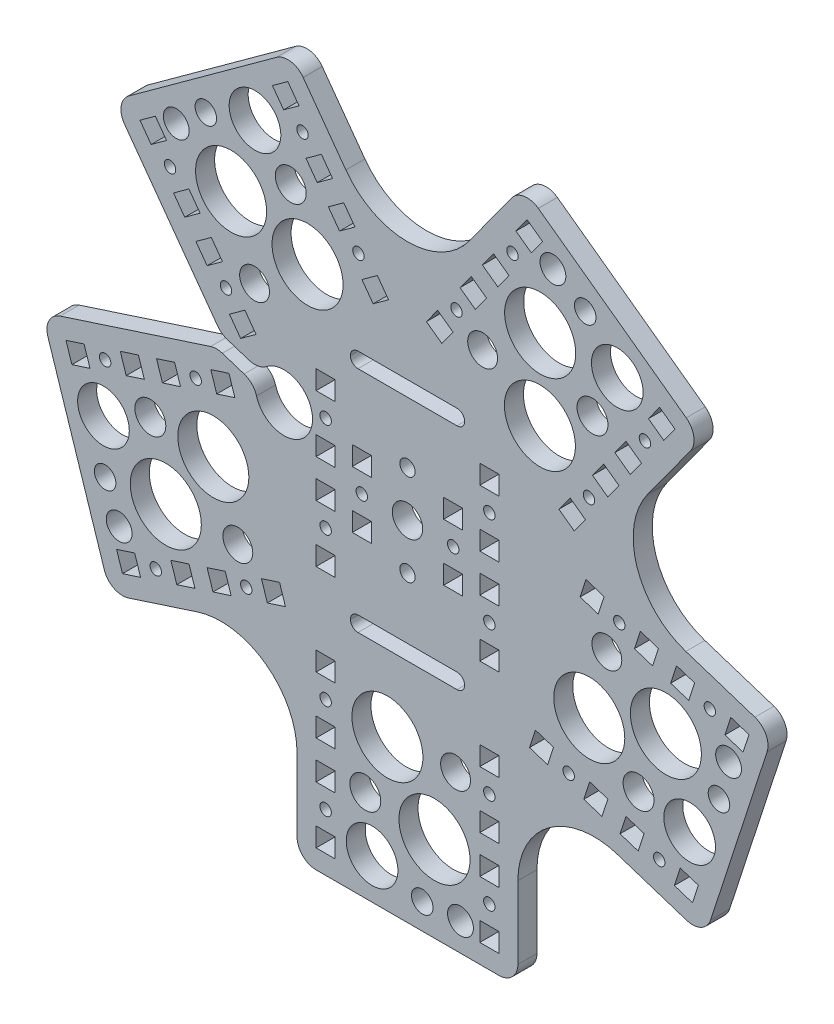
SolidWorks part; units mm, degrees
ref_plane "Plan de face" through (0, 0, 0) normal (0, 0, 1) x (1, 0, 0)
ref_plane "Plan de dessus" through (0, 0, 0) normal (0, 1, 0) x (1, 0, 0)
ref_plane "Plan de droite" through (0, 0, 0) normal (1, 0, 0) x (0, 0, -1)
sketch "Esquisse1" plane through (0, 0, 0) normal (0, 0, 1) x (1, 0, 0)
  line L0 (0, 0) -> (17.8582, 0) construction
  line L1 (-20, 40) -> (20, 40) construction
  line L2 (20, 40) -> (20, -40) construction
  line L3 (20, -40) -> (-20, -40) construction
  line L4 (-20, -40) -> (-20, 40) construction
  line L13 (0, 0) -> (0, 13.4404) construction
  line L16 (-20, -40) -> (-20, 40) construction
  line L18 (0, -40) -> (0, 40) construction
  line L19 (-15, -32) -> (-15, -28)
  line L20 (-15, 32) -> (15, 32)
  line L21 (-15, 32) -> (-15, 28)
  line L22 (-15, 28) -> (15, 28)
  line L23 (15, 32) -> (15, 28)
  line L24 (-15, -28) -> (15, -28)
  line L25 (15, -32) -> (15, -28)
  line L26 (-15, -32) -> (15, -32)
  line L27 (-29, -91.5) -> (29, -91.5)
  line L28 (29, -91.5) -> (29, -39.9151)
  line L29 (-29, -91.5) -> (-29, -39.9151)
  line L30 (-78.0602, -55.8557) -> (-29, -39.9151)
  line L31 (-95.9832, -0.6944) -> (-78.0602, -55.8557)
  line L32 (-95.9832, -0.6944) -> (-46.923, 15.2462) construction
  line L33 (-77.2438, 56.9793) -> (-46.923, 15.2462) construction
  line L34 (-30.3209, 91.0708) -> (-77.2438, 56.9793)
  line L35 (-30.3209, 91.0708) -> (0, 49.3377)
  line L36 (30.3209, 91.0708) -> (0, 49.3377)
  line L37 (77.2438, 56.9793) -> (30.3209, 91.0708)
  line L38 (77.2438, 56.9793) -> (46.923, 15.2462)
  line L39 (95.9832, -0.6944) -> (46.923, 15.2462)
  line L40 (78.0602, -55.8557) -> (95.9832, -0.6944)
  line L41 (78.0602, -55.8557) -> (29, -39.9151)
  line L42 (-15, 40) -> (15, 40) construction
  line L43 (-15, 40) -> (-15, 36) construction
  line L44 (-15, 36) -> (15, 36) construction
  line L45 (15, 40) -> (15, 36) construction
  line L46 (-15, -40) -> (-15, -36) construction
  line L47 (-15, -40) -> (15, -40) construction
  line L48 (15, -40) -> (15, -36) construction
  line L49 (-15, -36) -> (15, -36) construction
  line L50 (-77.2438, 56.9793) -> (-48.923, 17.999)
  line L51 (-48.923, 17.999) -> (-38.6965, 14.6762)
  line L52 (-38.6965, 14.6762) -> (-39.9326, 10.872) construction
  line L53 (-39.9326, 10.872) -> (-50.1591, 14.1947)
  line L54 (-50.1591, 14.1947) -> (-95.9832, -0.6944)
  line L55 (-46.923, 15.2462) -> (-39.3145, 12.7741) construction
  arc A0 (-38.6965, 14.6762) -> (-39.9326, 10.872) centre (-32.4399, 10.5404) cw
  circle A1 centre (0, 0) radius 4
  circle A2 centre (12, 0) radius 2 construction
  circle A3 centre (0, -12) radius 2
  circle A4 centre (-12, 0) radius 2 construction
  circle A5 centre (0, 12) radius 2
  circle A6 centre (-5.2713, -51.9057) radius 9.3306
  circle A7 centre (7.0906, -69.0484) radius 9.3306
  circle A8 centre (-9.3008, -80.9322) radius 6.7851
  circle A9 centre (-11.0766, -67.4093) radius 4.0624
  circle A10 centre (12.6227, -50.9495) radius 3.924
  circle A11 centre (3.8806, -84.7569) radius 2.83
  circle A12 centre (13.9204, -84.1422) radius 3.3916
  circle A13 centre (-75.7223, -39.2404) radius 3.3916
  circle A14 centre (-79.4094, -29.882) radius 2.83
  circle A15 centre (-79.8452, -16.1638) radius 6.7851
  circle A16 centre (-67.5329, -10.2962) radius 4.0624
  circle A17 centre (-50.9942, -11.0265) radius 9.3306
  circle A18 centre (-44.5553, -27.7492) radius 3.924
  circle A19 centre (-63.4778, -28.0807) radius 9.3306
  circle A20 centre (-60.7194, 59.8903) radius 3.3916
  circle A21 centre (-52.9583, 66.2888) radius 2.83
  circle A22 centre (-40.0462, 70.9424) radius 6.7851
  circle A23 centre (-30.661, 61.0459) radius 4.0624
  circle A24 centre (-26.2449, 45.091) radius 9.3306
  circle A25 centre (-40.1594, 33.7996) radius 3.924
  circle A26 centre (-46.3221, 51.6936) radius 9.3306
  circle A27 centre (38.1957, 76.2547) radius 3.3916
  circle A28 centre (46.6794, 70.8507) radius 2.83
  circle A29 centre (55.0953, 60.0086) radius 6.7851
  circle A30 centre (48.5833, 48.0246) radius 4.0624
  circle A31 centre (34.774, 38.8942) radius 9.3306
  circle A32 centre (19.7354, 48.6385) radius 3.924
  circle A33 centre (34.8492, 60.0291) radius 9.3306
  circle A34 centre (84.3256, -12.7623) radius 3.3916
  circle A35 centre (81.8078, -22.5006) radius 2.83
  circle A36 centre (74.097, -33.855) radius 6.7851
  circle A37 centre (60.6872, -31.3651) radius 4.0624
  circle A38 centre (47.7363, -21.053) radius 9.3306
  circle A39 centre (52.3565, -3.7394) radius 3.924
  circle A40 centre (67.8601, -14.5936) radius 9.3306
  point P12 (0, 0)
  point P19 (0, 0)
  point P32 (-37.6183, 51.7771)
  point P42 (0, 0)
  point P56 (0, 0)
  point P64 (0, 0)
  point P85 (0, 0)
  point P134 (0, 0)
  line B0 (-24, -71.5) -> (-24, -66.5)
  line B1 (-24, -71.5) -> (-19, -71.5)
  line B2 (-19, -71.5) -> (-19, -66.5)
  line B3 (-24, -66.5) -> (-19, -66.5)
  line B4 (-24, -81.5) -> (-24, -86.5)
  line B5 (-24, -81.5) -> (-19, -81.5)
  line B6 (-19, -81.5) -> (-19, -86.5)
  line B7 (-24, -86.5) -> (-19, -86.5)
  circle B8 centre (-21.5, -76.5) radius 1.5
  line B9 (-24, -56.5) -> (-24, -61.5)
  line B10 (-24, -56.5) -> (-19, -56.5)
  line B11 (-19, -56.5) -> (-19, -61.5)
  line B12 (-24, -61.5) -> (-19, -61.5)
  line B13 (-24, -46.5) -> (-24, -41.5)
  line B14 (-24, -46.5) -> (-19, -46.5)
  line B15 (-19, -46.5) -> (-19, -41.5)
  line B16 (-24, -41.5) -> (-19, -41.5)
  circle B17 centre (-21.5, -51.5) radius 1.5
  line B18 (24, -56.5) -> (24, -61.5)
  line B19 (24, -56.5) -> (19, -56.5)
  line B20 (19, -56.5) -> (19, -61.5)
  line B21 (24, -61.5) -> (19, -61.5)
  line B22 (24, -46.5) -> (24, -41.5)
  line B23 (24, -46.5) -> (19, -46.5)
  line B24 (19, -46.5) -> (19, -41.5)
  line B25 (24, -41.5) -> (19, -41.5)
  circle B26 centre (21.5, -51.5) radius 1.5
  line B27 (24, -71.5) -> (24, -66.5)
  line B28 (24, -71.5) -> (19, -71.5)
  line B29 (19, -71.5) -> (19, -66.5)
  line B30 (24, -66.5) -> (19, -66.5)
  line B31 (24, -81.5) -> (24, -86.5)
  line B32 (24, -81.5) -> (19, -81.5)
  line B33 (19, -81.5) -> (19, -86.5)
  line B34 (24, -86.5) -> (19, -86.5)
  circle B35 centre (21.5, -76.5) radius 1.5
  line B36 (24, -86.5) -> (-24, -86.5) construction
  line B37 (0, -86.5) -> (0, -41.5) construction
  line B38 (-75.4169, 0.7306) -> (-70.6617, 2.2757)
  line B39 (-75.4169, 0.7306) -> (-73.8719, -4.0246)
  line B40 (-73.8719, -4.0246) -> (-69.1166, -2.4796)
  line B41 (-70.6617, 2.2757) -> (-69.1166, -2.4796)
  line B42 (-84.9275, -2.3595) -> (-89.6828, -3.9046)
  line B43 (-84.9275, -2.3595) -> (-83.3824, -7.1148)
  line B44 (-83.3824, -7.1148) -> (-88.1377, -8.6599)
  line B45 (-89.6828, -3.9046) -> (-88.1377, -8.6599)
  circle B46 centre (-79.3997, -3.1921) radius 1.5
  line B47 (-61.1511, 5.3659) -> (-65.9064, 3.8208)
  line B48 (-61.1511, 5.3659) -> (-59.606, 0.6106)
  line B49 (-59.606, 0.6106) -> (-64.3613, -0.9345)
  line B50 (-65.9064, 3.8208) -> (-64.3613, -0.9345)
  line B51 (-51.6405, 8.4561) -> (-46.8853, 10.0012)
  line B52 (-51.6405, 8.4561) -> (-50.0955, 3.7008)
  line B53 (-50.0955, 3.7008) -> (-45.3402, 5.2459)
  line B54 (-46.8853, 10.0012) -> (-45.3402, 5.2459)
  circle B55 centre (-55.6233, 4.5333) radius 1.5
  line B56 (-46.3183, -40.2848) -> (-51.0736, -41.8299)
  line B57 (-46.3183, -40.2848) -> (-47.8634, -35.5295)
  line B58 (-47.8634, -35.5295) -> (-52.6187, -37.0746)
  line B59 (-51.0736, -41.8299) -> (-52.6187, -37.0746)
  line B60 (-36.8077, -37.1946) -> (-32.0524, -35.6496)
  line B61 (-36.8077, -37.1946) -> (-38.3528, -32.4394)
  line B62 (-38.3528, -32.4394) -> (-33.5975, -30.8943)
  line B63 (-32.0524, -35.6496) -> (-33.5975, -30.8943)
  circle B64 centre (-42.3355, -36.3621) radius 1.5
  line B65 (-60.5841, -44.9201) -> (-55.8289, -43.375)
  line B66 (-60.5841, -44.9201) -> (-62.1292, -40.1648)
  line B67 (-62.1292, -40.1648) -> (-57.3739, -38.6197)
  line B68 (-55.8289, -43.375) -> (-57.3739, -38.6197)
  line B69 (-70.0947, -48.0102) -> (-74.85, -49.5553)
  line B70 (-70.0947, -48.0102) -> (-71.6398, -43.255)
  line B71 (-71.6398, -43.255) -> (-76.3951, -44.8)
  line B72 (-74.85, -49.5553) -> (-76.3951, -44.8)
  circle B73 centre (-66.112, -44.0875) radius 1.5
  line B74 (-22.6102, 71.9516) -> (-19.6713, 67.9065)
  line B75 (-22.6102, 71.9516) -> (-26.6553, 69.0126)
  line B76 (-26.6553, 69.0126) -> (-23.7164, 64.9675)
  line B77 (-19.6713, 67.9065) -> (-23.7164, 64.9675)
  line B78 (-28.4881, 80.0417) -> (-31.427, 84.0868)
  line B79 (-28.4881, 80.0417) -> (-32.5332, 77.1028)
  line B80 (-32.5332, 77.1028) -> (-35.4721, 81.1479)
  line B81 (-31.427, 84.0868) -> (-35.4721, 81.1479)
  circle B82 centre (-27.5717, 74.5272) radius 1.5
  line B83 (-13.7935, 59.8163) -> (-16.7324, 63.8614)
  line B84 (-13.7935, 59.8163) -> (-17.8385, 56.8774)
  line B85 (-17.8385, 56.8774) -> (-20.7775, 60.9225)
  line B86 (-16.7324, 63.8614) -> (-20.7775, 60.9225)
  line B87 (-7.9156, 51.7261) -> (-4.9767, 47.6811)
  line B88 (-7.9156, 51.7261) -> (-11.9607, 48.7872)
  line B89 (-11.9607, 48.7872) -> (-9.0218, 44.7421)
  line B90 (-4.9767, 47.6811) -> (-9.0218, 44.7421)
  circle B91 centre (-12.8771, 54.3018) radius 1.5
  line B92 (-52.6263, 31.6026) -> (-55.5652, 35.6477)
  line B93 (-52.6263, 31.6026) -> (-48.5812, 34.5415)
  line B94 (-48.5812, 34.5415) -> (-51.5201, 38.5866)
  line B95 (-55.5652, 35.6477) -> (-51.5201, 38.5866)
  line B96 (-46.7484, 23.5124) -> (-43.8095, 19.4674)
  line B97 (-46.7484, 23.5124) -> (-42.7033, 26.4514)
  line B98 (-42.7033, 26.4514) -> (-39.7644, 22.4063)
  line B99 (-43.8095, 19.4674) -> (-39.7644, 22.4063)
  circle B100 centre (-47.6648, 29.027) radius 1.5
  line B101 (-61.4431, 43.7379) -> (-58.5041, 39.6928)
  line B102 (-61.4431, 43.7379) -> (-57.398, 46.6768)
  line B103 (-57.398, 46.6768) -> (-54.459, 42.6317)
  line B104 (-58.5041, 39.6928) -> (-54.459, 42.6317)
  line B105 (-67.3209, 51.828) -> (-70.2598, 55.8731)
  line B106 (-67.3209, 51.828) -> (-63.2758, 54.767)
  line B107 (-63.2758, 54.767) -> (-66.2147, 58.8121)
  line B108 (-70.2598, 55.8731) -> (-66.2147, 58.8121)
  circle B109 centre (-62.3594, 49.2524) radius 1.5
  line B110 (61.4431, 43.7379) -> (58.5041, 39.6928)
  line B111 (61.4431, 43.7379) -> (57.398, 46.6768)
  line B112 (57.398, 46.6768) -> (54.459, 42.6317)
  line B113 (58.5041, 39.6928) -> (54.459, 42.6317)
  line B114 (67.3209, 51.828) -> (70.2598, 55.8731)
  line B115 (67.3209, 51.828) -> (63.2758, 54.767)
  line B116 (63.2758, 54.767) -> (66.2147, 58.8121)
  line B117 (70.2598, 55.8731) -> (66.2147, 58.8121)
  circle B118 centre (62.3594, 49.2524) radius 1.5
  line B119 (52.6263, 31.6026) -> (55.5652, 35.6477)
  line B120 (52.6263, 31.6026) -> (48.5812, 34.5415)
  line B121 (48.5812, 34.5415) -> (51.5201, 38.5866)
  line B122 (55.5652, 35.6477) -> (51.5201, 38.5866)
  line B123 (46.7484, 23.5124) -> (43.8095, 19.4674)
  line B124 (46.7484, 23.5124) -> (42.7033, 26.4514)
  line B125 (42.7033, 26.4514) -> (39.7644, 22.4063)
  line B126 (43.8095, 19.4674) -> (39.7644, 22.4063)
  circle B127 centre (47.6648, 29.027) radius 1.5
  line B128 (13.7935, 59.8163) -> (16.7324, 63.8614)
  line B129 (13.7935, 59.8163) -> (17.8385, 56.8774)
  line B130 (17.8385, 56.8774) -> (20.7775, 60.9225)
  line B131 (16.7324, 63.8614) -> (20.7775, 60.9225)
  line B132 (7.9156, 51.7261) -> (4.9767, 47.6811)
  line B133 (7.9156, 51.7261) -> (11.9607, 48.7872)
  line B134 (11.9607, 48.7872) -> (9.0218, 44.7421)
  line B135 (4.9767, 47.6811) -> (9.0218, 44.7421)
  circle B136 centre (12.8771, 54.3018) radius 1.5
  line B137 (22.6102, 71.9516) -> (19.6713, 67.9065)
  line B138 (22.6102, 71.9516) -> (26.6553, 69.0126)
  line B139 (26.6553, 69.0126) -> (23.7164, 64.9675)
  line B140 (19.6713, 67.9065) -> (23.7164, 64.9675)
  line B141 (28.4881, 80.0417) -> (31.427, 84.0868)
  line B142 (28.4881, 80.0417) -> (32.5332, 77.1028)
  line B143 (32.5332, 77.1028) -> (35.4721, 81.1479)
  line B144 (31.427, 84.0868) -> (35.4721, 81.1479)
  circle B145 centre (27.5717, 74.5272) radius 1.5
  line B146 (60.5841, -44.9201) -> (55.8289, -43.375)
  line B147 (60.5841, -44.9201) -> (62.1292, -40.1648)
  line B148 (62.1292, -40.1648) -> (57.3739, -38.6197)
  line B149 (55.8289, -43.375) -> (57.3739, -38.6197)
  line B150 (70.0947, -48.0102) -> (74.85, -49.5553)
  line B151 (70.0947, -48.0102) -> (71.6398, -43.255)
  line B152 (71.6398, -43.255) -> (76.3951, -44.8)
  line B153 (74.85, -49.5553) -> (76.3951, -44.8)
  circle B154 centre (66.112, -44.0875) radius 1.5
  line B155 (46.3183, -40.2848) -> (51.0736, -41.8299)
  line B156 (46.3183, -40.2848) -> (47.8634, -35.5295)
  line B157 (47.8634, -35.5295) -> (52.6187, -37.0746)
  line B158 (51.0736, -41.8299) -> (52.6187, -37.0746)
  line B159 (36.8077, -37.1946) -> (32.0524, -35.6496)
  line B160 (36.8077, -37.1946) -> (38.3528, -32.4394)
  line B161 (38.3528, -32.4394) -> (33.5975, -30.8943)
  line B162 (32.0524, -35.6496) -> (33.5975, -30.8943)
  circle B163 centre (42.3355, -36.3621) radius 1.5
  line B164 (61.1511, 5.3659) -> (65.9064, 3.8208)
  line B165 (61.1511, 5.3659) -> (59.606, 0.6106)
  line B166 (59.606, 0.6106) -> (64.3613, -0.9345)
  line B167 (65.9064, 3.8208) -> (64.3613, -0.9345)
  line B168 (51.6405, 8.4561) -> (46.8853, 10.0012)
  line B169 (51.6405, 8.4561) -> (50.0955, 3.7008)
  line B170 (50.0955, 3.7008) -> (45.3402, 5.2459)
  line B171 (46.8853, 10.0012) -> (45.3402, 5.2459)
  circle B172 centre (55.6233, 4.5333) radius 1.5
  line B173 (75.4169, 0.7306) -> (70.6617, 2.2757)
  line B174 (75.4169, 0.7306) -> (73.8719, -4.0246)
  line B175 (73.8719, -4.0246) -> (69.1166, -2.4796)
  line B176 (70.6617, 2.2757) -> (69.1166, -2.4796)
  line B177 (84.9275, -2.3595) -> (89.6828, -3.9046)
  line B178 (84.9275, -2.3595) -> (83.3824, -7.1148)
  line B179 (83.3824, -7.1148) -> (88.1377, -8.6599)
  line B180 (89.6828, -3.9046) -> (88.1377, -8.6599)
  circle B181 centre (79.3997, -3.1921) radius 1.5
  line B182 (-24, -7.5) -> (-24, -2.5)
  line B183 (-24, -7.5) -> (-19, -7.5)
  line B184 (-19, -7.5) -> (-19, -2.5)
  line B185 (-24, -2.5) -> (-19, -2.5)
  line B186 (-24, -17.5) -> (-24, -22.5)
  line B187 (-24, -17.5) -> (-19, -17.5)
  line B188 (-19, -17.5) -> (-19, -22.5)
  line B189 (-24, -22.5) -> (-19, -22.5)
  circle B190 centre (-21.5, -12.5) radius 1.5
  line B191 (-24, 7.5) -> (-24, 2.5)
  line B192 (-24, 7.5) -> (-19, 7.5)
  line B193 (-19, 7.5) -> (-19, 2.5)
  line B194 (-24, 2.5) -> (-19, 2.5)
  line B195 (-24, 17.5) -> (-24, 22.5)
  line B196 (-24, 17.5) -> (-19, 17.5)
  line B197 (-19, 17.5) -> (-19, 22.5)
  line B198 (-24, 22.5) -> (-19, 22.5)
  circle B199 centre (-21.5, 12.5) radius 1.5
  line B200 (24, 7.5) -> (24, 2.5)
  line B201 (24, 7.5) -> (19, 7.5)
  line B202 (19, 7.5) -> (19, 2.5)
  line B203 (24, 2.5) -> (19, 2.5)
  line B204 (24, 17.5) -> (24, 22.5)
  line B205 (24, 17.5) -> (19, 17.5)
  line B206 (19, 17.5) -> (19, 22.5)
  line B207 (24, 22.5) -> (19, 22.5)
  circle B208 centre (21.5, 12.5) radius 1.5
  line B209 (24, -7.5) -> (24, -2.5)
  line B210 (24, -7.5) -> (19, -7.5)
  line B211 (19, -7.5) -> (19, -2.5)
  line B212 (24, -2.5) -> (19, -2.5)
  line B213 (24, -17.5) -> (24, -22.5)
  line B214 (24, -17.5) -> (19, -17.5)
  line B215 (19, -17.5) -> (19, -22.5)
  line B216 (24, -22.5) -> (19, -22.5)
  circle B217 centre (21.5, -12.5) radius 1.5
  line B218 (24, 22.5) -> (-24, 22.5) construction
  line B219 (24, -22.5) -> (-24, -22.5) construction
  line B220 (0, -22.5) -> (0, 22.5) construction
  line B221 (14.5, -5) -> (14.5, -10)
  line B222 (14.5, -5) -> (9.5, -5)
  line B223 (9.5, -5) -> (9.5, -10)
  line B224 (14.5, -10) -> (9.5, -10)
  line B225 (14.5, 5) -> (14.5, 10)
  line B226 (14.5, 5) -> (9.5, 5)
  line B227 (9.5, 5) -> (9.5, 10)
  line B228 (14.5, 10) -> (9.5, 10)
  line B229 (12, 0) -> (18.2802, 0) construction
  circle B230 centre (12, 0) radius 1.5
  line B231 (-12, -5) -> (-12, 5) construction
  line B232 (-9.5, -5) -> (-9.5, -10)
  line B233 (-9.5, -5) -> (-14.5, -5)
  line B234 (-14.5, -5) -> (-14.5, -10)
  line B235 (-9.5, -10) -> (-14.5, -10)
  line B236 (-9.5, 5) -> (-9.5, 10)
  line B237 (-9.5, 5) -> (-14.5, 5)
  line B238 (-14.5, 5) -> (-14.5, 10)
  line B239 (-9.5, 10) -> (-14.5, 10)
  line B240 (-12, 0) -> (-5.7198, 0) construction
  circle B241 centre (-12, 0) radius 1.5
  dimension "D2" = 5
  dimension "D9" = 4
  dimension "D14" = 7.5
  dimension "D17" = 8
  dimension "D18" = 4
  dimension "D4" = 8
  dimension "D5" = 5
  dimension "D6" = 5
  dimension "D7" = 4
  dimension "D8" = 20
  dimension "D10" = 5
  dimension "D11" = 4
  dimension "D12" = 5
  dimension "D3" = 5
  dimension "D13" = 64
  dimension "D15" = 8
  dimension "D16" = 28
  dimension "D19" = 12
  dimension "D20" = 4
  dimension "D21" = 5
sketch_block_instance "Bloc1-4"
sketch_block "Bloc1"
sketch_block_instance "Trou M3 plots 5mm-54"
sketch_block "Trou M3 plots 5mm" parameters "D2"=3, "D1"=5, "D3"=5, "D4"=8
sketch_block_instance "Trou M3 plots 5mm-56"
sketch_block_instance "Trou M3 plots 5mm-55"
sketch_block_instance "Trou M3 plots 5mm-52"
sketch_block_instance "Bloc1-5"
sketch_block_instance "Bloc1-6"
sketch_block_instance "Bloc1-7"
sketch_block_instance "Bloc1-8"
sketch_block_instance "Bloc1-10"
sketch_block_instance "Trou M3 plots 5mm-61"
sketch_block_instance "Trou M3 plots 5mm-62"
extrude "Boss.-Extru.1" add sketch "Esquisse1" along normal blind 5
fillet "Congé1" radius 2 8 edges at (-15, -32, 2.5) (-15, -28, 2.5) (15, -28, 2.5) (15, -32, 2.5) (15, 28, 2.5) (15, 32, 2.5) (-15, 28, 2.5) (-15, 32, 2.5)
fillet "Congé2" radius 20 4 edges at (29, -39.9151, 2.5) (-29, -39.9151, 2.5) (0, 49.3377, 2.5) (46.923, 15.2462, 2.5)
fillet "Congé3" radius 5 14 edges at (-78.0602, -55.8557, 2.5) (-29, -91.5, 2.5) (29, -91.5, 2.5) (-30.3209, 91.0708, 2.5) (78.0602, -55.8557, 2.5) (95.9832, -0.6944, 2.5) (77.2438, 56.9793, 2.5) (30.3209, 91.0708, 2.5) (-48.923, 17.999, 2.5) (-50.1591, 14.1947, 2.5) (-39.9326, 10.872, 2.5) (-38.6965, 14.6762, 2.5) (-95.9832, -0.6944, 2.5) (-77.2438, 56.9793, 2.5)
